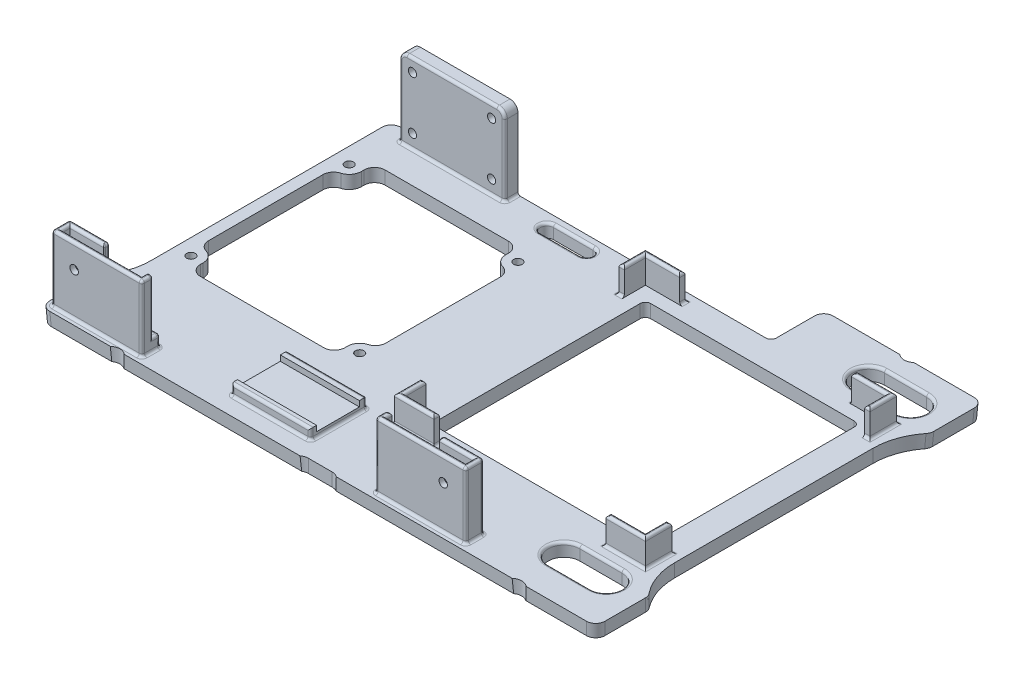
SolidWorks part; units mm, degrees
ref_plane "Front Plane" through (0, 0, 0) normal (0, 0, 1) x (1, 0, 0)
ref_plane "Top Plane" through (0, 0, 0) normal (0, 1, 0) x (1, 0, 0)
ref_plane "Right Plane" through (0, 0, 0) normal (1, 0, 0) x (0, 0, -1)
sketch "Sketch1" plane through (0, 0, 0) normal (0, 1, 0) x (1, 0, 0)
  line L1 (105, -73.25) -> (-105, -73.25)
  line L2 (105, -73.25) -> (105, 73.25)
  line L3 (105, 73.25) -> (-105, 73.25)
  line L4 (-105, -73.25) -> (-105, 73.25)
  line L5 (105, -73.25) -> (-105, 73.25) construction
  line L6 (105, 73.25) -> (-105, -73.25) construction
  point P0 (0, 0)
  dimension "D1" = 210
  dimension "D2" = 146.5
extrude "Boss-Extrude1" add sketch "Sketch1" along normal blind 5
draft "Draft2" type of draft neutral plane draft angle 3 faces to draft 4 face at (105, 2.5, 0) face at (0, 2.5, -73.25) face at (-105, 2.5, 0) face at (0, 2.5, 73.25) neutral plane through (0, 0, 0) neutral plane normal (0, -1, 0) parameters "D1"=3
sketch "Sketch2" plane through (0, 5, 0) normal (0, 1, 0) x (1, 0, 0)
  line L0 (105.262, 73.512) -> (-105.262, 73.512) construction
  line L1 (-105.262, 73.512) -> (44.738, 73.512)
  line L2 (-105.262, 73.512) -> (-105.262, 53.512)
  line L3 (-99.262, 53.512) -> (44.738, 53.512)
  line L4 (44.738, 73.512) -> (44.738, 53.512)
  line L5 (73.5547, 73.512) -> (78.8453, 73.512)
  line L6 (105.262, -73.512) -> (105.262, 73.512) construction
  line L7 (105.262, 53.4453) -> (105.262, 48.1547) construction
  line L9 (105.262, -48.1547) -> (105.262, -53.4453) construction
  line L10 (-105.262, -73.512) -> (105.262, -73.512) construction
  line L11 (101.728, -73.5319) -> (-101.728, -73.5319) construction
  line L12 (73.5324, -73.5319) -> (78.8453, -73.512)
  line L14 (-8.0753, -75.1328) -> (8.0753, -75.1328)
  line L15 (-78.8453, -73.512) -> (-73.5547, -73.512)
  line L16 (-105.262, 73.512) -> (-105.262, -73.512) construction
  line L17 (-105.262, -48.1547) -> (-105.262, -53.4453) construction
  line L18 (4.541, -72.7185) -> (-4.541, -72.7185)
  line L19 (-105.262, 2.6453) -> (-105.262, -2.6453) construction
  line L20 (-34.762, 48.012) -> (-19.762, 48.012) construction
  line L25 (-29.262, -28.488) -> (-93.262, -28.488) construction
  line L26 (-29.262, -28.488) -> (-29.262, 31.512) construction
  line L27 (-29.262, 31.512) -> (-93.262, 31.512) construction
  line L28 (-93.262, -28.488) -> (-93.262, 31.512) construction
  line L29 (-29.262, -28.488) -> (-93.262, 31.512) construction
  line L30 (-29.262, 31.512) -> (-93.262, -28.488) construction
  line L31 (-34.762, 50.512) -> (-19.762, 50.512)
  line L32 (-34.762, 45.512) -> (-19.762, 45.512)
  line L33 (75.738, 59.512) -> (91.738, 59.512) construction
  line L34 (75.738, 65.512) -> (91.738, 65.512)
  line L35 (75.738, 53.512) -> (91.738, 53.512)
  line L36 (75.738, -56.012) -> (91.738, -56.012) construction
  line L37 (75.738, -50.012) -> (91.738, -50.012)
  line L38 (75.738, -62.012) -> (91.738, -62.012)
  line L40 (-94.887, -24.1578) -> (-94.887, 27.1819)
  line L42 (-27.637, 27.1819) -> (-27.637, -24.1578)
  line L47 (-84.637, -33.488) -> (-37.887, -33.488)
  line L48 (-88.637, -28.488) -> (-88.637, -29.488)
  line L49 (-33.887, -29.488) -> (-33.887, -28.488)
  line L50 (-88.637, 31.512) -> (-88.637, 32.512)
  line L51 (-33.887, 31.512) -> (-33.887, 32.512)
  line L52 (-84.637, 36.512) -> (-37.887, 36.512)
  line L53 (99.262, 37.567) -> (99.262, -37.567)
  line L54 (105.262, -53.4453) -> (105.262, 53.4453)
  line L55 (-99.262, 53.512) -> (-99.262, -37.567)
  line L57 (-105.262, 53.512) -> (-105.262, -53.4453)
  arc A0 (78.8453, 73.512) -> (73.5547, 73.512) centre (76.2, 76.5125) cw
  arc A1 (73.6532, 75.3634) -> (76.2, 73.7185) centre (76.2, 76.5125) ccw construction
  arc A2 (105.262, 53.4453) -> (105.262, 48.1547) centre (108.2625, 50.8) ccw construction
  arc A3 (107.1134, 53.3468) -> (107.1134, 48.2532) centre (108.2625, 50.8) ccw construction
  arc A5 (-105.262, -53.4453) -> (-99.262, -37.567) centre (-123.2721, -37.567) ccw
  arc A6 (105.262, -48.1547) -> (105.262, -53.4453) centre (108.2625, -50.8) ccw construction
  arc A7 (107.1134, -48.2532) -> (107.1134, -53.3468) centre (108.2625, -50.8) ccw construction
  arc A8 (78.8453, -73.512) -> (73.5324, -73.5319) centre (76.2, -76.5125) ccw
  arc A9 (78.7468, -75.3634) -> (73.6532, -75.3634) centre (76.2, -76.5125) ccw construction
  arc A10 (-73.5547, -73.512) -> (-78.8453, -73.512) centre (-76.2, -76.5125) ccw
  arc A11 (-73.6532, -75.3634) -> (-78.7468, -75.3634) centre (-76.2, -76.5125) ccw construction
  arc A12 (-105.262, -53.4453) -> (-105.262, -48.1547) centre (-108.2625, -50.8) ccw construction
  arc A13 (-107.1134, -53.3468) -> (-107.1134, -48.2532) centre (-108.2625, -50.8) ccw construction
  arc A14 (-105.262, -2.6453) -> (-105.262, 2.6453) centre (-108.2625, 0) ccw construction
  arc A15 (-107.1134, -2.5468) -> (-107.1134, 2.5468) centre (-108.2625, 0) ccw construction
  arc A16 (-4.541, -72.7185) -> (-8.0753, -75.1328) centre (-4.541, -76.5125) ccw
  arc A17 (-4.541, -72.7185) -> (-8.0753, -75.1328) centre (-4.541, -76.5125) ccw
  circle A18 centre (-93.262, 31.512) radius 1.625
  arc A19 (8.0753, -75.1328) -> (4.541, -72.7185) centre (4.541, -76.5125) ccw
  arc A20 (8.0753, -75.1328) -> (4.541, -72.7185) centre (4.541, -76.5125) ccw
  circle A21 centre (-29.262, 31.512) radius 1.625
  circle A22 centre (-29.262, -28.488) radius 1.625
  circle A23 centre (-93.262, -28.488) radius 1.625
  arc A24 (-27.637, -24.1578) -> (-33.887, -28.488) centre (-29.262, -28.488) ccw
  arc A26 (-34.762, 50.512) -> (-34.762, 45.512) centre (-34.762, 48.012) ccw
  arc A27 (-19.762, 45.512) -> (-19.762, 50.512) centre (-19.762, 48.012) ccw
  arc A28 (75.738, 65.512) -> (75.738, 53.512) centre (75.738, 59.512) ccw
  arc A29 (91.738, 53.512) -> (91.738, 65.512) centre (91.738, 59.512) ccw
  arc A30 (75.738, -50.012) -> (75.738, -62.012) centre (75.738, -56.012) ccw
  arc A31 (91.738, -62.012) -> (91.738, -50.012) centre (91.738, -56.012) ccw
  arc A35 (-88.637, -28.488) -> (-94.887, -24.1578) centre (-93.262, -28.488) ccw
  arc A36 (-33.887, 31.512) -> (-27.637, 27.1819) centre (-29.262, 31.512) ccw
  arc A37 (-94.887, 27.1819) -> (-88.637, 31.512) centre (-93.262, 31.512) ccw
  arc A42 (-84.637, -33.488) -> (-88.637, -29.488) centre (-84.637, -29.488) cw
  arc A43 (-37.887, -33.488) -> (-33.887, -29.488) centre (-37.887, -29.488) ccw
  arc A44 (-88.637, 32.512) -> (-84.637, 36.512) centre (-84.637, 32.512) cw
  arc A45 (-33.887, 32.512) -> (-37.887, 36.512) centre (-37.887, 32.512) ccw
  arc A46 (105.262, 53.4453) -> (99.262, 37.567) centre (123.2721, 37.567) ccw
  arc A47 (99.262, -37.567) -> (105.262, -53.4453) centre (123.2721, -37.567) ccw
  point P71 (83.738, 59.512)
  point P73 (-61.262, 1.512)
  point P88 (-27.262, 48.012)
  point P93 (-27.262, 53.512)
  point P99 (83.738, -56.012)
  dimension "D3" = 4
  dimension "D4" = 1
  dimension "D5" = 3.25
  dimension "D6" = 1
  dimension "D7" = 15
  dimension "D8" = 2.5
  dimension "D11" = 6
  dimension "D18" = 4
  dimension "D20" = 3
  dimension "D2" = 20
  dimension "D9" = 3
  dimension "D10" = 25
  dimension "D12" = 16
  dimension "D13" = 6
  dimension "15" = 11.5
  dimension "D14" = 14
  dimension "D15" = 12
  dimension "D16" = 64
  dimension "D17" = 60
  dimension "D19" = 5
  dimension "D21" = 6
  dimension "D22" = 150
extrude "Cut-Extrude1" cut sketch "Sketch2" against normal through all
sketch "Sketch4" plane through (0, 5, 0) normal (0, 1, 0) x (1, 0, 0)
  line L0 (-88.4811, -66.412) -> (-87.462, -64.412)
  line L1 (-87.462, -64.412) -> (-103.262, -64.412)
  line L2 (-103.262, -64.412) -> (-103.262, -71.312)
  line L3 (-103.262, -71.312) -> (-69.062, -71.312)
  line L4 (-69.062, -71.312) -> (-69.062, -67.012)
  line L5 (-69.062, -67.012) -> (-71.062, -67.012)
  line L6 (-71.062, -67.012) -> (-71.062, -69.312)
  line L7 (-71.062, -69.312) -> (-73.912, -69.312)
  line L8 (-73.912, -69.312) -> (-73.912, -67.012) construction
  line L9 (-73.912, -67.012) -> (-76.912, -67.012) construction
  line L10 (-76.912, -67.012) -> (-76.912, -69.312) construction
  line L11 (-76.912, -69.312) -> (-79.512, -69.312)
  line L12 (-79.512, -69.312) -> (-79.512, -67.012) construction
  line L13 (-79.512, -67.012) -> (-82.512, -67.012) construction
  line L14 (-82.512, -67.012) -> (-82.512, -69.312) construction
  line L15 (-82.512, -69.312) -> (-101.262, -69.312)
  line L16 (-101.262, -69.312) -> (-101.262, -66.412)
  line L17 (-101.262, -66.412) -> (-88.4811, -66.412)
  line L19 (-82.512, -69.312) -> (-79.512, -69.312)
  line L38 (-105.262, -73.512) -> (-78.8453, -73.512) construction
  line L39 (-105.262, -53.4453) -> (-105.262, -73.512) construction
  line L40 (-24.762, -114.0747) -> (-24.762, -51.4081) construction
  line L42 (-76.912, -69.312) -> (-73.912, -69.312)
  line L43 (32.988, -67.012) -> (32.988, -69.312) construction
  line L44 (29.988, -67.012) -> (32.988, -67.012) construction
  line L45 (29.988, -69.312) -> (29.988, -67.012) construction
  line L46 (27.388, -67.012) -> (27.388, -69.312) construction
  line L47 (24.388, -67.012) -> (27.388, -67.012) construction
  line L48 (24.388, -69.312) -> (24.388, -67.012) construction
  line L49 (27.388, -69.312) -> (24.388, -69.312)
  line L50 (32.988, -69.312) -> (29.988, -69.312)
  line L51 (51.738, -66.412) -> (38.957, -66.412)
  line L52 (51.738, -69.312) -> (51.738, -66.412)
  line L53 (32.988, -69.312) -> (51.738, -69.312)
  line L54 (27.388, -69.312) -> (29.988, -69.312)
  line L55 (21.538, -69.312) -> (24.388, -69.312)
  line L56 (21.538, -67.012) -> (21.538, -69.312)
  line L57 (19.538, -67.012) -> (21.538, -67.012)
  line L58 (19.538, -71.312) -> (19.538, -67.012)
  line L59 (53.738, -71.312) -> (19.538, -71.312)
  line L60 (53.738, -64.412) -> (53.738, -71.312)
  line L61 (37.938, -64.412) -> (53.738, -64.412)
  line L62 (38.957, -66.412) -> (37.938, -64.412)
  dimension "D1" = 117
  dimension "D2" = 2
  dimension "D3" = 2
  dimension "D4" = 2
  dimension "D5" = 2.9
  dimension "D6" = 2
  dimension "D7" = 34.2
  dimension "D8" = 2.3
  dimension "D9" = 2.85
  dimension "D10" = 2.6
  dimension "D11" = 3
  dimension "D12" = 15.8
  dimension "D13" = 2.2
  dimension "D14" = 2
  dimension "D15" = 153
extrude "Boss-Extrude2" add sketch "Sketch4" along normal blind 25
sketch "Sketch6" plane through (0, 5, 0) normal (0, 1, 0) x (1, 0, 0)
  line L1 (-103.262, -71.312) -> (-69.062, -71.312)
  line L2 (-103.262, -71.312) -> (-103.262, -64.412)
  line L3 (-103.262, -64.412) -> (-69.062, -64.412)
  line L4 (-69.062, -71.312) -> (-69.062, -64.412)
  line L7 (53.738, -71.312) -> (19.538, -71.312)
  line L8 (53.738, -71.312) -> (53.738, -64.412)
  line L9 (53.738, -64.412) -> (19.538, -64.412)
  line L10 (19.538, -71.312) -> (19.538, -64.412)
  line L13 (-103.262, -71.312) -> (-69.062, -71.312) construction
  line L14 (-103.262, -64.412) -> (-103.262, -71.312) construction
  line L15 (-87.462, -64.412) -> (-103.262, -64.412) construction
  line L16 (-69.062, -71.312) -> (-69.062, -67.012) construction
  line L17 (53.738, -71.312) -> (19.538, -71.312) construction
  line L18 (53.738, -64.412) -> (53.738, -71.312) construction
  line L19 (37.938, -64.412) -> (53.738, -64.412) construction
  line L20 (19.538, -71.312) -> (19.538, -67.012) construction
extrude "Boss-Extrude3" add sketch "Sketch6" along normal up to surface (4.54 mm away)
sketch "Sketch7" plane through (0, 5, 0) normal (0, 1, 0) x (1, 0, 0)
  line L0 (33.738, -47.837) -> (-83.262, -47.837) construction
  line L1 (-9.762, -66.637) -> (-39.762, -66.637)
  line L2 (-9.762, -66.637) -> (-9.762, -45.337)
  line L3 (-9.762, -45.337) -> (-39.762, -45.337)
  line L4 (-39.762, -66.637) -> (-39.762, -45.337)
  line L5 (-9.762, -66.637) -> (-39.762, -45.337) construction
  line L6 (-9.762, -45.337) -> (-39.762, -66.637) construction
  line L10 (33.738, -64.137) -> (-83.262, -64.137) construction
  line L11 (-24.762, -83.222) -> (-24.762, -45.052) construction
  point P0 (-24.762, -55.987)
  dimension "D1" = 2.5
  dimension "D2" = 30
  dimension "D3" = 2.5
extrude "Boss-Extrude4" add sketch "Sketch7" along normal blind 4
sketch "Sketch8" plane through (-39.762, 0, 0) normal (-1, 0, 0) x (0, 0, 1)
  line L0 (45.337, 9) -> (66.637, 9) construction
  line L1 (48.2046, 9) -> (64.232, 9) construction
  line L2 (48.2046, 9) -> (48.2046, 7) construction
  line L3 (48.2046, 7) -> (64.232, 7) construction
  line L4 (64.232, 9) -> (64.232, 7) construction
  line L5 (48.2046, 7) -> (48.2046, 62.88) construction
  line L6 (64.232, 7) -> (48.2046, 7) construction
  line L7 (64.232, 9.54) -> (64.232, 7) construction
  line L8 (48.1046, 9.1) -> (64.332, 9.1)
  line L9 (64.332, 9.1) -> (64.332, 6.9)
  line L10 (48.1046, 6.9) -> (64.332, 6.9)
  line L11 (48.1046, 9.1) -> (48.1046, 6.9)
  point P6 (56.2183, 9)
  point P7 (56.2183, 7)
  dimension "D1" = 0.1
extrude "Cut-Extrude2" cut sketch "Sketch8" against normal up to next
sketch "Sketch9" plane through (0, 0, 71.312) normal (0, 0, 1) x (1, 0, 0)
  circle A0 centre (-94.737, 22.04) radius 2.54 construction
  circle A1 centre (-94.7101, 22.24) radius 2.54 construction
  circle A2 centre (45.213, 22.04) radius 2.54 construction
  circle A3 centre (46.0059, 22.24) radius 2.54 construction
  circle A4 centre (-94.737, 21.1) radius 1.6
  circle A5 centre (45.213, 21.1) radius 1.6
  circle A6 centre (45.213, 22.04) radius 2.5 construction
  circle A7 centre (-94.737, 22.04) radius 2.5 construction
  dimension "D1" = 3.2
extrude "Cut-Extrude3" cut sketch "Sketch9" against normal through all and the other way through all
sketch "Sketch10" plane through (0, 5, 0) normal (0, 1, 0) x (1, 0, 0)
  line L0 (80.762, 48.012) -> (93.762, 48.012)
  line L1 (93.762, 48.012) -> (93.762, 40.012)
  line L2 (93.762, 40.012) -> (95.762, 40.012)
  line L3 (95.762, 40.012) -> (95.762, 50.012)
  line L4 (95.762, 50.012) -> (80.762, 50.012)
  line L5 (80.762, 50.012) -> (80.762, 48.012)
  line L6 (48.177, 59.2421) -> (48.177, -51.6629) construction
  line L7 (48.177, 21.2167) -> (48.177, -16.3626) construction
  line L8 (124.5659, 2.427) -> (-8.4192, 2.427) construction
  line L9 (29.3874, 2.427) -> (66.9667, 2.427) construction
  line L16 (80.2805, 47.512) -> (92.754, 47.512) construction
  line L22 (15.592, -43.158) -> (2.592, -43.158)
  line L27 (80.762, -45.158) -> (80.762, -43.158)
  line L28 (95.762, -45.158) -> (80.762, -45.158)
  line L29 (95.762, -35.158) -> (95.762, -45.158)
  line L30 (93.762, -35.158) -> (95.762, -35.158)
  line L31 (93.762, -43.158) -> (93.762, -35.158)
  line L32 (80.762, -43.158) -> (93.762, -43.158)
  line L33 (93.262, 47.004) -> (93.262, -42.15) construction
  line L35 (2.592, -43.158) -> (2.592, -35.158)
  line L36 (2.592, -35.158) -> (0.592, -35.158)
  line L37 (0.592, -35.158) -> (0.592, -45.158)
  line L38 (0.592, -45.158) -> (15.592, -45.158)
  line L39 (15.592, -45.158) -> (15.592, -43.158)
  line L40 (15.592, 50.012) -> (15.592, 48.012)
  line L41 (0.592, 50.012) -> (15.592, 50.012)
  line L42 (0.592, 40.012) -> (0.592, 50.012)
  line L43 (2.592, 40.012) -> (0.592, 40.012)
  line L44 (2.592, 48.012) -> (2.592, 40.012)
  line L45 (15.592, 48.012) -> (2.592, 48.012)
  dimension "D1" = 2
  dimension "D2" = 15
  dimension "D3" = 10
  dimension "D4" = 0.5
  dimension "D5" = 0.5
extrude "Boss-Extrude5" add sketch "Sketch10" along normal blind 10
sketch "Sketch13" plane through (0, 5, 0) normal (0, 1, 0) x (1, 0, 0)
  line L0 (93.762, -35.158) -> (93.762, -43.158) construction
  line L1 (88.762, 43.012) -> (7.592, 43.012)
  line L2 (88.762, 43.012) -> (88.762, -38.158)
  line L3 (88.762, -38.158) -> (7.592, -38.158)
  line L4 (7.592, 43.012) -> (7.592, -38.158)
  line L5 (93.762, -43.158) -> (80.762, -43.158) construction
  line L6 (80.762, 48.012) -> (93.762, 48.012) construction
  point P10 (87.262, 48.012)
  dimension "D1" = 5
  dimension "D2" = 5
  dimension "D3" = 5
extrude "Cut-Extrude5" cut sketch "Sketch13" against normal through all
sketch "Sketch14" plane through (0, 5, 0) normal (0, 1, 0) x (1, 0, 0)
  line L0 (-37.262, 48.012) -> (-105.262, 48.012) construction
  line L1 (-105.262, -53.4453) -> (-105.262, -73.512) construction
  line L2 (-99.262, 53.512) -> (44.738, 53.512) construction
  line L3 (-91.262, 53.512) -> (-51.262, 53.512)
  line L4 (-91.262, 53.512) -> (-91.262, 48.512)
  line L5 (-91.262, 48.512) -> (-51.262, 48.512)
  line L6 (-51.262, 53.512) -> (-51.262, 48.512)
  arc A0 (-34.762, 50.512) -> (-34.762, 45.512) centre (-34.762, 48.012) ccw construction
  point P14 (-71.262, 48.012)
  point P15 (-71.262, 48.512)
  dimension "D1" = 40
  dimension "D2" = 5
extrude "Boss-Extrude6" add sketch "Sketch14" along normal blind 30
sketch "Sketch15" plane through (0, 0, -53.512) normal (0, 0, -1) x (-1, 0, 0)
  line L1 (86.262, 10.2) -> (56.262, 10.2) construction
  line L2 (86.262, 10.2) -> (86.262, 30.2) construction
  line L3 (86.262, 30.2) -> (56.262, 30.2) construction
  line L4 (56.262, 10.2) -> (56.262, 30.2) construction
  line L5 (86.262, 10.2) -> (56.262, 30.2) construction
  line L6 (86.262, 30.2) -> (56.262, 10.2) construction
  circle A0 centre (56.262, 30.2) radius 2.8
  circle A1 centre (86.262, 30.2) radius 2.8
  circle A2 centre (56.262, 10.2) radius 2.8
  circle A3 centre (86.262, 10.2) radius 2.8
  circle A4 centre (56.262, 30.2) radius 1.65 construction
  circle A5 centre (86.262, 10.2) radius 1.65 construction
  point P0 (71.262, 20.2)
  dimension "D1" = 5.6
extrude "Cut-Extrude6" cut sketch "Sketch15" against normal blind 2
sketch "Sketch16" plane through (0, 0, -53.512) normal (0, 0, -1) x (-1, 0, 0)
  line L1 (86.262, 10.2) -> (56.262, 10.2) construction
  line L2 (86.262, 10.2) -> (86.262, 30.2) construction
  line L3 (86.262, 30.2) -> (56.262, 30.2) construction
  line L4 (56.262, 10.2) -> (56.262, 30.2) construction
  line L5 (86.262, 10.2) -> (56.262, 30.2) construction
  line L6 (86.262, 30.2) -> (56.262, 10.2) construction
  circle A0 centre (56.262, 30.2) radius 1.55
  circle A1 centre (86.262, 30.2) radius 1.55
  circle A2 centre (86.262, 10.2) radius 1.55
  circle A3 centre (56.262, 10.2) radius 1.55
  circle A5 centre (56.262, 30.2) radius 2.8 construction
  circle A6 centre (86.262, 10.2) radius 2.8 construction
  point P0 (71.262, 20.2)
  dimension "D1" = 3.1
extrude "Cut-Extrude7" cut sketch "Sketch16" against normal up to next
fillet "Fillet3" radius 1 79 edges at (87.262, 15, 43.158) (93.762, 15, 39.158) (94.762, 15, 35.158) (95.762, 15, 40.158) (88.262, 15, -50.012) (95.762, 15, -45.012) (94.762, 15, -40.012) (80.762, 15, -49.012) (1.592, 15, 35.158) (-39.762, 7, 66.637) (-9.762, 7, 45.337) (-9.762, 7, 66.637) (19.538, 19.77, 67.012) (19.538, 9.54, 65.712) (19.538, 17.5, 71.312) (53.738, 17.5, 71.312) (53.738, 17.5, 64.412) (19.538, 7.27, 64.412) (-69.062, 19.77, 67.012) (-103.262, 17.5, 64.412) (-24.762, 9, 45.337) (-69.062, 5, 67.862) (-103.262, 5, 67.862) (-86.162, 5, 64.412) (-24.762, 5, 66.637) (-24.762, 5, 45.337) (36.638, 5, 64.412) (53.738, 5, 67.862) (94.762, 5, 35.158) (95.762, 5, 40.158) (88.262, 5, 45.158) (80.762, 5, 44.158) (94.762, 5, -40.012) (95.762, 5, -45.012) (88.262, 5, -50.012) (1.592, 5, 35.158) (45.838, 30, 64.412) (53.738, 30, 67.862) (36.638, 30, 71.312) (19.538, 30, 69.162) (20.538, 30, 67.012) (45.3475, 30, 66.412) (-86.162, 30, 69.312) (-71.062, 30, 68.162) (-70.062, 30, 67.012) (-69.062, 30, 69.162) (-103.262, 30, 67.862) (-95.362, 30, 64.412) (-87.9716, 30, 65.412) (-101.262, 30, 67.862) (36.638, 30, 69.312) (51.738, 30, 67.862) (37.938, 19.77, 64.412) (0.592, 15, 40.158) (9.092, 15, 43.158) (15.592, 15, 44.158) (15.592, 15, -49.012) (2.592, 15, -44.012) (1.592, 15, -40.012) (8.092, 15, -50.012) (8.092, 5, -50.012) (0.592, 5, -45.012) (1.592, 5, -40.012) (15.592, 5, 44.158) (8.092, 5, 45.158) (-51.262, 20, -48.512) (-91.262, 20, -48.512) (-51.262, 5, -51.012) (-71.262, 5, -48.512) (-91.262, 5, -51.012) (-37.262, 5, -48.012) (-27.262, 5, -50.512) (69.738, 5, -59.512) (83.738, 5, -65.512) (97.738, 5, -59.512) (83.738, 5, 62.012) (83.738, 5, 50.012) (-27.262, 5, -45.512) (97.738, 5, 56.012)
fillet "Fillet5" radius 4 4 edges at (-27.637, 2.5, 24.1578) (-94.887, 2.5, 24.1578) (-27.637, 2.5, -27.1819) (-94.887, 2.5, -27.1819)
fillet "Fillet2" radius 2 5 edges at (44.738, 2.5, -53.512) (7.592, 2.5, 38.158) (88.762, 2.5, 38.158) (88.762, 2.5, -43.012) (7.592, 2.5, -43.012)
fillet "Fillet1" radius 3.5 8 edges at (105.131, 2.5, -73.381) (105.131, 2.5, 73.381) (-105.131, 2.5, 73.381) (44.738, 2.5, -73.381) (105.1304, 2.488, -53.2947) (105.1304, 2.488, 53.2947) (-99.262, 2.5, -53.512) (-105.1304, 2.488, 53.2947)
fillet "Fillet6" radius 3 4 edges at (-90.9691, 34.7071, -48.8049) (-51.5549, 34.7071, -48.8049) (-51.262, 35, -51.512) (-91.262, 35, -51.512)
